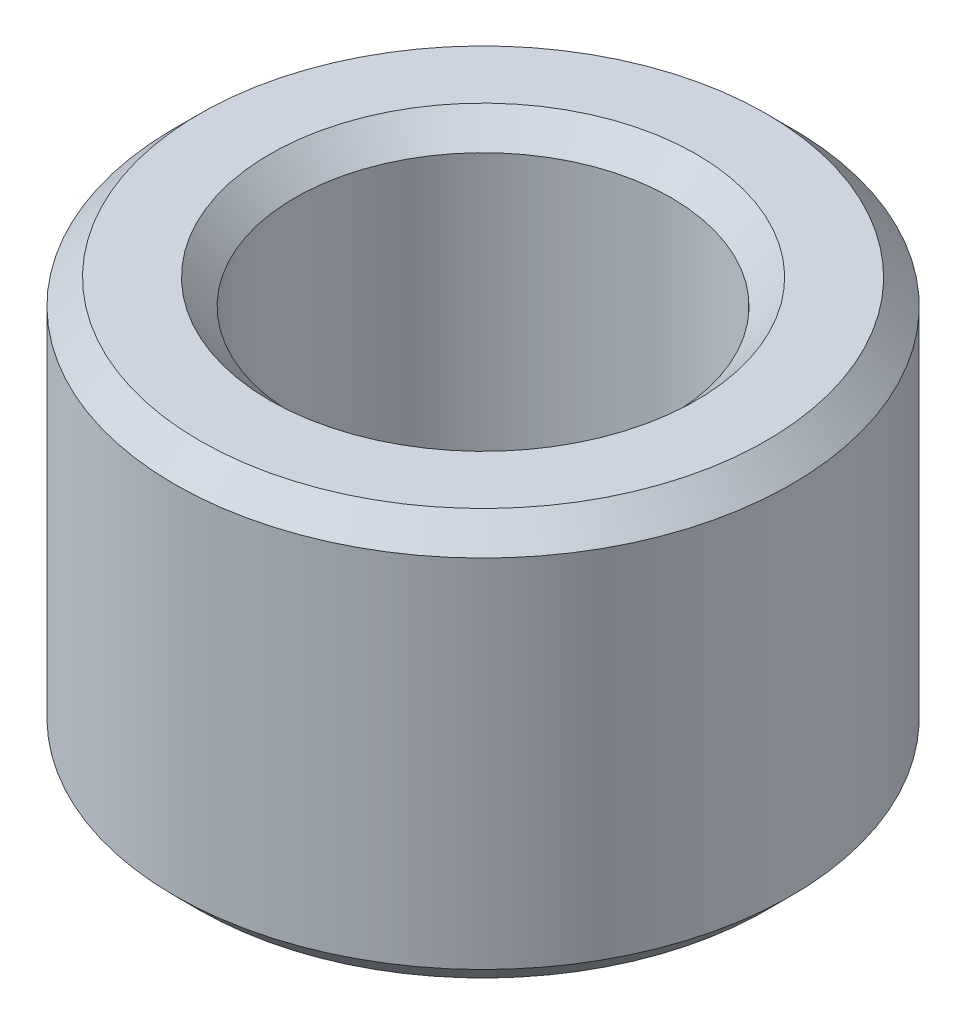
SolidWorks part; units mm, degrees
ref_plane "Front Plane" through (0, 0, 0) normal (0, 0, 1) x (1, 0, 0)
ref_plane "Top Plane" through (0, 0, 0) normal (0, 1, 0) x (1, 0, 0)
ref_plane "Right Plane" through (0, 0, 0) normal (1, 0, 0) x (0, 0, -1)
sketch "Sketch1" plane through (0, 0, 0) normal (0, 1, 0) x (1, 0, 0)
  circle A0 centre (0, 0) radius 47.5
  dimension "SLEEVE_OD" = 95
extrude "Boss-Extrude1" add sketch "Sketch1" along normal blind 62.6268
sketch "Sketch2" plane through (0, 0, 0) normal (0, 1, 0) x (1, 0, 0)
  circle A0 centre (0, 0) radius 28.9703
  dimension "BORE_D" = 57.9407
extrude "Cut-Extrude1" cut sketch "Sketch2" along normal through all
chamfer "Chamfer1" distance 3.8746 angle 45 4 edges at (0, 62.6268, 28.9703) (0, 0, 28.9703) (0, 0, 47.5) (0, 62.6268, 47.5)
